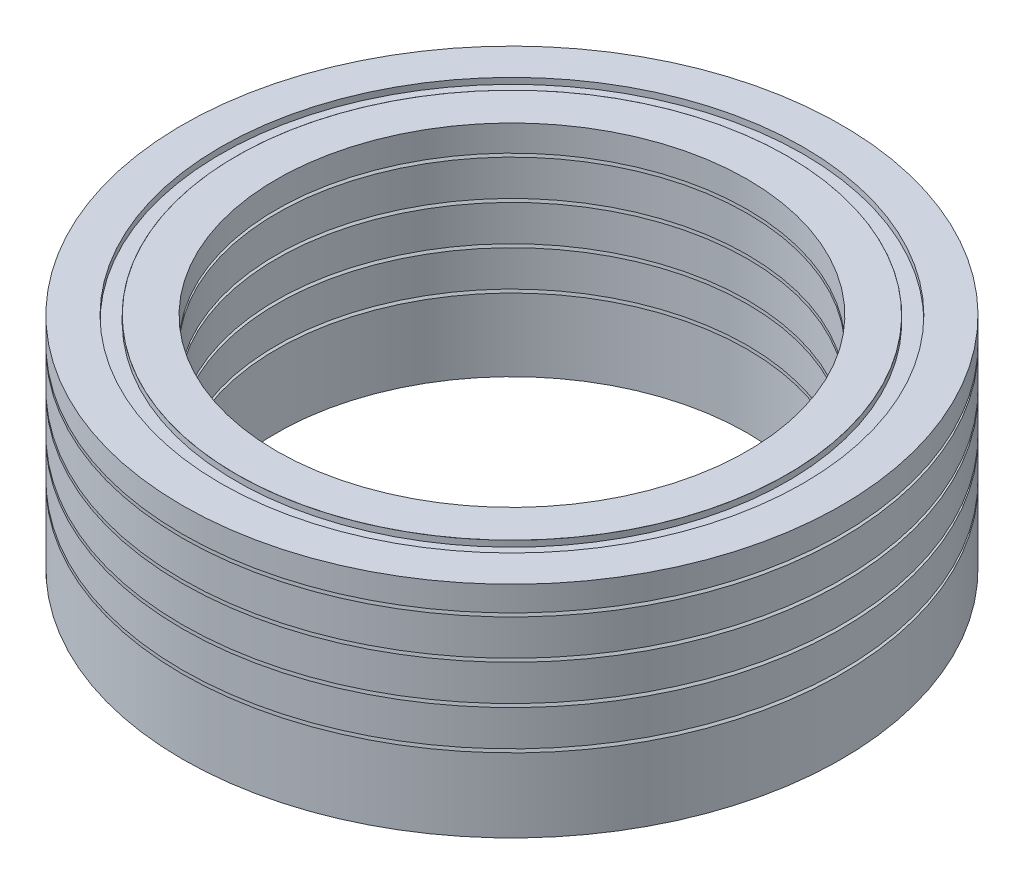
SolidWorks part; units mm, degrees
ref_plane "Front" through (0, 0, 0) normal (0, 0, 1) x (1, 0, 0)
ref_plane "Top" through (0, 0, 0) normal (0, 1, 0) x (1, 0, 0)
ref_plane "Right" through (0, 0, 0) normal (1, 0, 0) x (0, 0, -1)
ref_axis "Axis1" through (-84.4107, 0, 0) along (1, 0, 0)
ref_axis "Axis2" through (0, 64.3378, 0) along (0, -1, 0)
ref_axis "Axis3" through (0, 0, -102.329) along (0, 0, 1)
sketch "Sketch1" plane through (0, 0, 0) normal (0, 1, 0) x (1, 0, 0)
  circle A0 centre (0, 0) radius 21
extrude "Extrude1" add sketch "Sketch1" along normal blind 14
sketch "Sketch2" plane through (0, 0, 0) normal (0, 1, 0) x (1, 0, 0)
  circle A0 centre (0, 0) radius 15
extrude "Cut-Extrude1" cut sketch "Sketch2" along normal blind 14
sketch "Sketch3" plane through (0, 0, 0) normal (1, 0, 0) x (0, 0, -1)
  line L0 (0, 0) -> (0, 19.0632) construction
  line L1 (-21.2998, 12.5616) -> (-18.0563, 11)
  line L2 (-18.0563, 11) -> (-14.2166, 12.6776)
  line L3 (-14.2166, 12.6776) -> (-14.2166, 12.4593)
  line L4 (-14.2166, 12.4593) -> (-17.5604, 10.9984)
  line L5 (-18.5604, 11.0207) -> (-21.2998, 12.3396)
  line L6 (-21.2998, 12.3396) -> (-21.2998, 10.0616)
  line L7 (-18.5604, 11.0207) -> (-18.5604, 10.614)
  line L8 (-18.5604, 10.614) -> (-17.5604, 10.614)
  line L9 (-17.5604, 10.614) -> (-17.5604, 10.9984)
  line L10 (21, 14) -> (-21, 14) construction
  line L11 (-21.2998, 10.0616) -> (-18.0563, 8.5)
  line L12 (-18.0563, 8.5) -> (-14.2166, 10.1776)
  line L13 (-14.2166, 10.1776) -> (-14.2166, 9.9593)
  line L14 (-14.2166, 9.9593) -> (-17.5604, 8.4984)
  line L15 (-18.5604, 8.5207) -> (-21.2998, 9.8396)
  line L16 (-21.5626, 12.4661) -> (-21.5626, 12.6881) [skipped]
  line L17 (-18.5604, 8.5207) -> (-18.5604, 8.114)
  line L18 (-18.5604, 8.114) -> (-17.5604, 8.114)
  line L19 (-17.5604, 8.114) -> (-17.5604, 8.4984)
  line L20 (-21.2998, 7.5616) -> (-18.0563, 6)
  line L21 (-18.0563, 6) -> (-14.2166, 7.6776)
  line L22 (-14.2166, 7.6776) -> (-14.2166, 7.4593)
  line L23 (-14.2166, 7.4593) -> (-17.5604, 5.9984)
  line L24 (-18.5604, 6.0207) -> (-21.2998, 7.3396)
  line L25 (-21.5626, 9.9661) -> (-21.5626, 10.1881) [skipped]
  line L26 (-18.5604, 6.0207) -> (-18.5604, 5.614)
  line L27 (-18.5604, 5.614) -> (-17.5604, 5.614)
  line L28 (-17.5604, 5.614) -> (-17.5604, 5.9984)
  line L29 (-21.2998, 5.0616) -> (-18.0563, 3.5)
  line L30 (-18.0563, 3.5) -> (-14.2166, 5.1776)
  line L31 (-14.2166, 5.1776) -> (-14.2166, 4.9593)
  line L32 (-14.2166, 4.9593) -> (-17.5604, 3.4984)
  line L33 (-18.5604, 3.5207) -> (-21.2998, 4.8396)
  line L34 (-21.5626, 7.4661) -> (-21.5626, 7.6881) [skipped]
  line L35 (-18.5604, 3.5207) -> (-18.5604, 3.114)
  line L36 (-18.5604, 3.114) -> (-17.5604, 3.114)
  line L37 (-17.5604, 3.114) -> (-17.5604, 3.4984)
  line L38 (-21.5626, 4.9661) -> (-21.5626, 5.1881) [skipped]
  line L39 (-21.2998, 16.7578) -> (-21.9542, 16.7578)
  line L40 (-21.2998, 16.7578) -> (-21.2998, 15.6776)
  line L41 (-21.2998, 4.4499) -> (-21.9542, 4.4499)
  line L42 (-21.9542, 16.7578) -> (-21.9542, 4.4499)
  line L43 (-21.2998, 9.8396) -> (-21.2998, 7.5616)
  line L44 (-21.2998, 7.3396) -> (-21.2998, 5.0616)
  line L45 (-21.2998, 4.8396) -> (-21.2998, 4.4499)
  line L62 (-14.2166, 15.6776) -> (-21.2998, 15.6776)
  line L63 (-21.2998, 15.5616) -> (-18.0563, 14) [skipped]
  line L64 (-14.2166, 15.6776) -> (-14.2166, 15.4593)
  line L65 (-14.2166, 15.4593) -> (-17.5604, 13.9984)
  line L66 (-18.5604, 14.0207) -> (-21.2998, 15.3396)
  line L67 (-18.5604, 14.0207) -> (-18.5604, 13.614)
  line L68 (-18.5604, 13.614) -> (-17.5604, 13.614)
  line L69 (-17.5604, 13.614) -> (-17.5604, 13.9984)
  line L87 (-21.2998, 15.3396) -> (-21.2998, 12.5616)
  line L88 (-18.0563, 14) -> (-14.2166, 15.6776) [skipped]
  dimension "D1" = 0.2
  dimension "D2" = 0.2
  dimension "D3" = 1
  dimension "D4" = 3
revolve "Cut-Revolve1" cut sketch "Sketch3" angle 360 about L0
